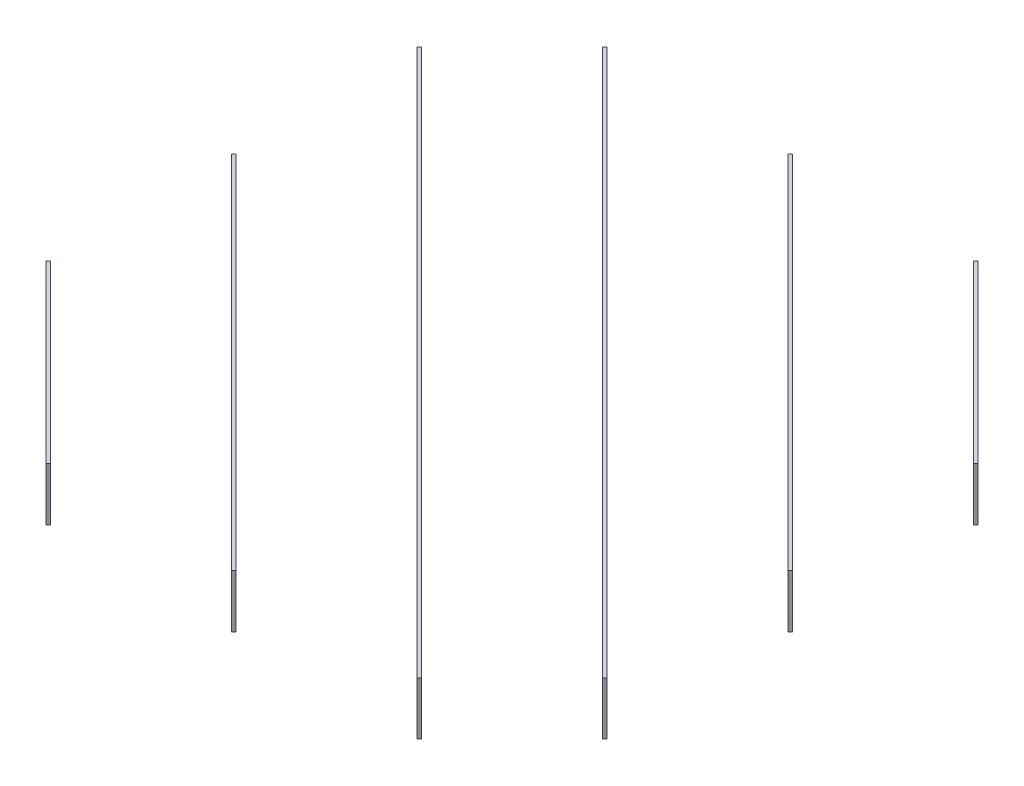
SolidWorks part; units mm, degrees
material "Plain Carbon Steel"
ref_plane "Front" through (0, 0, 0) normal (0, 0, 1) x (1, 0, 0)
ref_plane "Top" through (0, 0, 0) normal (0, 1, 0) x (1, 0, 0)
ref_plane "Right" through (0, 0, 0) normal (1, 0, 0) x (0, 0, -1)
sketch "Sketch1" plane through (0, 0, 0) normal (0, 1, 0) x (1, 0, 0)
  line L0 (-525, -525) -> (-525, 525) construction
  line L1 (-605, 605) -> (605, 605) construction
  line L2 (-605, 605) -> (-605, -605) construction
  line L3 (-605, -605) -> (605, -605) construction
  line L4 (605, 605) -> (605, -605) construction
  line L5 (-605, 605) -> (605, -605) construction
  line L6 (-605, -605) -> (605, 605) construction
  line L7 (-525, 525) -> (525, 525) construction
  line L8 (-525, 350) -> (525, 350) construction
  line L9 (-525, 175) -> (525, 175) construction
  line L10 (-525, 0) -> (525, 0) construction
  line L11 (-525, -175) -> (525, -175) construction
  line L12 (-525, -350) -> (525, -350) construction
  line L13 (-525, -525) -> (525, -525) construction
  line L14 (-350, -525) -> (-350, 525) construction
  line L15 (-175, -525) -> (-175, 525) construction
  line L16 (0, -525) -> (0, 525) construction
  line L17 (175, -525) -> (175, 525) construction
  line L18 (350, -525) -> (350, 525) construction
  line L19 (525, -525) -> (525, 525) construction
  line L20 (525, -525) -> (0, -1050) construction
  line L21 (0, -1050) -> (-525, -525) construction
  line L22 (0, -1050) -> (0, 0) construction
  point P0 (0, 0)
  dimension "D1" = 1210
  dimension "D2" = 1210
  dimension "D5" = 175
  dimension "D3" = 7
  dimension "D4" = 7
sketch "Sketch2" plane through (0, 0, 0) normal (0, 1, 0) x (1, 0, 0)
  line L0 (-605, -274.2426) -> (-274.2426, -605)
  line L1 (-602.8787, 602.8787) -> (602.8787, 602.8787) construction
  line L2 (-602.8787, 602.8787) -> (-602.8787, -602.8787) construction
  line L3 (-602.8787, -602.8787) -> (602.8787, -602.8787) construction
  line L4 (602.8787, 602.8787) -> (602.8787, -602.8787) construction
  line L5 (-602.8787, 602.8787) -> (602.8787, -602.8787) construction
  line L6 (-602.8787, -602.8787) -> (602.8787, 602.8787) construction
  line L7 (-605, 605) -> (605, -605) construction
  line L8 (-427.8787, 602.8787) -> (602.8787, -427.8787) construction
  line L9 (-77.8787, 602.8787) -> (602.8787, -77.8787) construction
  line L10 (272.1213, 602.8787) -> (602.8787, 272.1213) construction
  line L11 (-602.8787, -272.1213) -> (-272.1213, -602.8787) construction
  line L12 (-602.8787, 77.8787) -> (77.8787, -602.8787) construction
  line L13 (-602.8787, 427.8787) -> (427.8787, -602.8787) construction
  line L14 (-605, 75.7574) -> (75.7574, -605)
  line L15 (-605, 425.7574) -> (425.7574, -605)
  line L16 (-430, 600.7574) -> (600.7574, -430)
  line L17 (-80, 600.7574) -> (600.7574, -80)
  line L18 (270, 600.7574) -> (600.7574, 270)
  line L19 (-600.7574, -270) -> (-270, -600.7574)
  line L20 (-600.7574, 80) -> (80, -600.7574)
  line L21 (-600.7574, 430) -> (430, -600.7574)
  line L22 (-425.7574, 605) -> (605, -425.7574)
  line L23 (-75.7574, 605) -> (605, -75.7574)
  line L24 (274.2426, 605) -> (605, 274.2426)
  line L25 (-605, -274.2426) -> (-600.7574, -270)
  line L26 (-274.2426, -605) -> (-270, -600.7574)
  line L27 (-605, 75.7574) -> (-600.7574, 80)
  line L28 (75.7574, -605) -> (80, -600.7574)
  line L29 (-605, 425.7574) -> (-600.7574, 430)
  line L30 (425.7574, -605) -> (430, -600.7574)
  line L31 (-430, 600.7574) -> (-425.7574, 605)
  line L32 (600.7574, -430) -> (605, -425.7574)
  line L33 (-80, 600.7574) -> (-75.7574, 605)
  line L34 (600.7574, -80) -> (605, -75.7574)
  line L35 (270, 600.7574) -> (274.2426, 605)
  line L36 (600.7574, 270) -> (605, 274.2426)
  line L38 (-605, 605) -> (605, 605) construction
  line L39 (605, 605) -> (605, -605) construction
extrude "Boss-Extrude1" add sketch "Sketch2" along normal blind 100
sketch "Sketch3" plane through (-439.6213, 0, 439.6213) normal (-0.7071, 0, 0.7071) x (0.7071, 0, 0.7071)
  line L0 (-742.4621, 0) -> (0, 0) construction
  line L1 (-126.7056, 50) -> (-120.7056, 50)
  line L2 (-126.7056, 50) -> (-126.7056, -50)
  line L3 (-126.7056, -50) -> (-120.7056, -50)
  line L4 (-120.7056, 50) -> (-120.7056, -50)
  line L5 (-126.7056, 50) -> (-120.7056, -50) construction
  line L6 (-126.7056, -50) -> (-120.7056, 50) construction
  line L7 (123.7437, 0) -> (-618.7184, 0) construction
  line L8 (-374.2311, 50) -> (-368.2311, 50)
  line L9 (-374.2311, 50) -> (-374.2311, -50)
  line L10 (-374.2311, -50) -> (-368.2311, -50)
  line L11 (-368.2311, 50) -> (-368.2311, -50)
  line L12 (-374.2311, 50) -> (-368.2311, -50) construction
  line L13 (-374.2311, -50) -> (-368.2311, 50) construction
  line L14 (-621.7184, 50) -> (-615.7184, 50)
  line L15 (-621.7184, 50) -> (-621.7184, -50)
  line L16 (-621.7184, -50) -> (-615.7184, -50)
  line L17 (-615.7184, 50) -> (-615.7184, -50)
  line L18 (-621.7184, 50) -> (-615.7184, -50) construction
  line L19 (-621.7184, -50) -> (-615.7184, 50) construction
  line L20 (0, 0) -> (0, 100) construction
  line L21 (-233.8808, 100) -> (233.8808, 100) construction
  line L22 (621.7184, -50) -> (615.7184, 50) construction
  line L23 (621.7184, 50) -> (615.7184, -50) construction
  line L24 (374.2311, -50) -> (368.2311, 50) construction
  line L25 (374.2311, 50) -> (368.2311, -50) construction
  line L26 (126.7056, -50) -> (120.7056, 50) construction
  line L27 (126.7056, 50) -> (120.7056, -50) construction
  line L28 (615.7184, 50) -> (615.7184, -50)
  line L29 (621.7184, -50) -> (615.7184, -50)
  line L30 (621.7184, 50) -> (621.7184, -50)
  line L31 (621.7184, 50) -> (615.7184, 50)
  line L32 (368.2311, 50) -> (368.2311, -50)
  line L33 (374.2311, -50) -> (368.2311, -50)
  line L34 (374.2311, 50) -> (374.2311, -50)
  line L35 (374.2311, 50) -> (368.2311, 50)
  line L36 (120.7056, 50) -> (120.7056, -50)
  line L37 (126.7056, -50) -> (120.7056, -50)
  line L38 (126.7056, 50) -> (126.7056, -50)
  line L39 (126.7056, 50) -> (120.7056, 50)
  circle A0 centre (-126.7056, 50) radius 1.5
  circle A1 centre (-120.7056, 50) radius 1.5
  circle A2 centre (-621.7184, 50) radius 1.5
  circle A3 centre (-615.7184, 50) radius 1.5
  circle A4 centre (-374.2311, 50) radius 1.5
  circle A5 centre (-368.2311, 50) radius 1.5
  circle A6 centre (368.2311, 50) radius 1.5
  circle A7 centre (374.2311, 50) radius 1.5
  circle A8 centre (615.7184, 50) radius 1.5
  circle A9 centre (621.7184, 50) radius 1.5
  circle A10 centre (120.7056, 50) radius 1.5
  circle A11 centre (126.7056, 50) radius 1.5
  point P0 (-123.7056, 0)
  point P7 (-371.2311, 0)
  point P12 (-618.7184, 0)
  point P48 (618.7184, 0)
  point P49 (371.2311, 0)
  point P50 (123.7056, 0)
  line M15 (-233.8808, 0) -> (233.8808, 0)
  dimension "D1" = 100
  dimension "D7" = 3
  dimension "D8" = 3
  dimension "D9" = 3
  dimension "D10" = 3
  dimension "D11" = 3
  dimension "D12" = 3
  dimension "D2" = 100
  dimension "D3" = 100
  dimension "D4" = 3
  dimension "D5" = 3
  dimension "D6" = 3
extrude "Cut-Extrude1" cut sketch "Sketch3" against normal through all contours A3 L14 A2 L15 L16 L17 | L14 A2 L15 | L17 A3 L14 | L14 A3 L17 | L15 A2 L14 | L8 A4 L9 | L9 A4 L8 | A5 L8 A4 L9 L10 L11 | L8 A5 L11 | L11 A5 L8 | L1 A0 L2 | L4 A1 L1 | L1 A1 L4 | A1 L1 A0 L2 L4 M15 | L2 A0 L1 | A10 L36 L39 | A10 L39 L36 | L38 A11 L39 A10 L36 M15 | A11 L38 L39 | A11 L39 L38 | A6 L32 L35 | L34 A7 L35 A6 L32 L33 | A7 L35 L34 | A7 L34 L35 | A6 L35 L32 | A8 L28 L31 | A9 L31 L30 | L30 A9 L31 A8 L28 L29 | A9 L30 L31 | A8 L31 L28 region at (-529.3657, 50.2122, 349.8769) region at (-528.7655, 49.3634, 350.4771) region at (-352.1483, 24.7096, 527.0944) region at (-527.0944, 24.7096, 352.1483) region at (-524.823, 50.2122, 354.4196) region at (-525.4232, 49.3634, 353.8194) region at (-354.4196, 50.2122, 524.823) region at (-353.8194, 49.3634, 525.4232) region at (-350.4771, 49.3634, 528.7655) region at (-349.8769, 50.2122, 529.3657) region at (-704.3927, 50.2122, 174.8499) region at (-703.7925, 49.3634, 175.4502) region at (-702.1213, -0.2925, 177.1213) region at (-699.8499, 50.2122, 179.3927) region at (-700.4502, 49.3634, 178.7925) region at (-879.3927, 50.2122, -0.1501) region at (-878.7925, 49.3634, 0.4502) region at (-877.1213, -0.2925, 2.1213) region at (-874.8499, 50.2122, 4.3927) region at (-875.4502, 49.3634, 3.7925) region at (-3.7925, 49.3634, 875.4502) region at (-4.3927, 50.2122, 874.8499) region at (-2.1213, -0.2925, 877.1213) region at (0.1501, 50.2122, 879.3927) region at (-0.4502, 49.3634, 878.7925) region at (-178.7925, 49.3634, 700.4502) region at (-179.3927, 50.2122, 699.8499) region at (-177.1213, -0.2925, 702.1213) region at (-174.8499, 50.2122, 704.3927) region at (-175.4502, 49.3634, 703.7925)
sketch "Sketch6" plane through (260.3787, 0, -260.3787) normal (-0.7071, 0, 0.7071) x (0.7071, 0, 0.7071)
  line L0 (-0.0191, 81) -> (-0.0191, 75) construction
  line L1 (14.9809, 81) -> (-15.0191, 81) construction
  line L2 (-15.0191, 75) -> (14.9809, 75) construction
  line L3 (24.9809, 75) -> (24.9809, 81) construction
  line L4 (-28.0191, 84) -> (27.9809, 84)
  line L5 (-28.0191, 84) -> (-28.0191, 72)
  line L6 (-28.0191, 72) -> (27.9809, 72)
  line L7 (27.9809, 84) -> (27.9809, 72)
  line L8 (-28.0191, 84) -> (27.9809, 72) construction
  line L9 (-28.0191, 72) -> (27.9809, 84) construction
  point P6 (-0.0191, 78)
  dimension "D1" = 3
  dimension "D2" = 3
extrude "Cut-Extrude3" cut sketch "Sketch6" against normal up to next (6 mm away)
sketch "Sketch7" plane through (-264.6213, 0, 264.6213) normal (-0.7071, 0, 0.7071) x (0.7071, 0, 0.7071)
  line L4 (27.9809, 84) -> (-28.0191, 84)
  line L5 (27.9809, 72) -> (27.9809, 84)
  line L6 (-28.0191, 72) -> (27.9809, 72)
  line L7 (-28.0191, 84) -> (-28.0191, 72)
  line L8 (27.9809, 84) -> (-28.0191, 84)
  line L9 (27.9809, 72) -> (27.9809, 84)
  line L10 (-28.0191, 72) -> (27.9809, 72)
  line L11 (-28.0191, 84) -> (-28.0191, 72)
  dimension "D1" = 0
extrude "Cut-Extrude4" cut sketch "Sketch7" against normal up to next (6 mm away)
sketch "Sketch8" plane through (-439.6213, 0, 439.6213) normal (-0.7071, 0, 0.7071) x (0.7071, 0, 0.7071)
  line L0 (-120.7056, 0) -> (120.7056, 0) construction
  circle A0 centre (0, 0) radius 1.5
  dimension "D1" = 3
extrude "Cut-Extrude5" cut sketch "Sketch8" against normal through all
sketch "Sketch9" plane through (-89.6213, 0, 89.6213) normal (-0.7071, 0, 0.7071) x (0.7071, 0, 0.7071)
  circle A0 centre (0, 16) radius 4
  circle A1 centre (0, 36) radius 4
  dimension "D1" = 8
extrude "Cut-Extrude6" cut sketch "Sketch9" against normal up to surface (253.4874 mm away) up to face at (89.6213, 33.4578, -89.6213)
ref_point "Point1"
sketch "Sketch10" plane through (439.6213, 0, -439.6213) normal (0.7071, 0, -0.7071) x (-0.7071, 0, -0.7071)
  line L0 (1.5, 0) -> (-1.5, 0) construction
  line L1 (0, 0) -> (0, 100) construction
  line L2 (-233.8808, 100) -> (233.8808, 100) construction
  circle A0 centre (0, 50) radius 3
  dimension "D1" = 6
extrude "Cut-Extrude7" cut sketch "Sketch10" against normal up to surface (253.4874 mm away) up to face at (260.3652, 78, -260.3922)
sketch "Sketch11" plane through (-439.6213, 0, 439.6213) normal (-0.7071, 0, 0.7071) x (0.7071, 0, 0.7071)
  circle A1 centre (0, 50) radius 3
  circle A2 centre (0, 50) radius 3
  dimension "D1" = 0
extrude "Cut-Extrude8" cut sketch "Sketch11" against normal up to surface (253.4874 mm away) up to face at (-260.3922, 78, 260.3652)
sketch "Sketch12" plane through (264.6213, 0, -264.6213) normal (0.7071, 0, -0.7071) x (-0.7071, 0, -0.7071)
  line L0 (368.2311, 0) -> (126.7056, 0) construction
  line L1 (126.7056, 0) -> (247.4683, 0) construction
  line L2 (247.4683, 0) -> (247.4683, 100) construction
  line L3 (-481.3681, 100) -> (481.3681, 100) construction
  circle A0 centre (247.4683, 50) radius 3
  dimension "D1" = 6
extrude "Cut-Extrude9" cut sketch "Sketch12" against normal up to surface (748.4621 mm away) up to face at (-266.7426, 50, 262.5)
sketch "Sketch13" plane through (89.6213, 0, -89.6213) normal (0.7071, 0, -0.7071) x (-0.7071, 0, -0.7071)
  line L0 (615.7184, 0) -> (374.2311, 0) construction
  line L1 (374.2311, 0) -> (494.9747, 0) construction
  line L2 (494.9747, 0) -> (494.9747, 100) construction
  line L3 (-728.8555, 100) -> (728.8555, 100) construction
  circle A0 centre (494.9747, 50) radius 3
  dimension "D1" = 6
extrude "Cut-Extrude10" cut sketch "Sketch13" against normal up to surface (253.4874 mm away) up to face at (-266.7292, 50, -87.4865)
ref_plane "Plane1" through (0, 0, 0) normal (0.7071, 0, 0.7071) x (0.7071, 0, -0.7071)
mirror "Mirror1" about plane through (0, 0, 0) normal (0.7071, 0, 0.7071) of "Cut-Extrude9", "Cut-Extrude10"
equation "\"Plate width\"= 100mm"
equation "\"D1@Boss-Extrude1\"=\"Plate width\""
equation "\"D1@Sketch3\"=\"Plate width\""
equation "\"D2@Sketch3\"=\"Plate width\""
equation "\"D3@Sketch3\"=\"Plate width\""
equation "\"D4@Sketch3\"=\"half plate thickness\""
equation "\"D5@Sketch3\"=\"half plate thickness\""
equation "\"D6@Sketch3\"=\"half plate thickness\""
equation "\"D7@Sketch3\"=\"half plate thickness\""
equation "\"D8@Sketch3\"=\"half plate thickness\""
equation "\"D9@Sketch3\"=\"half plate thickness\""
equation "\"D10@Sketch3\"=\"half plate thickness\""
equation "\"D11@Sketch3\"=\"half plate thickness\""
equation "\"D12@Sketch3\"=\"half plate thickness\""
